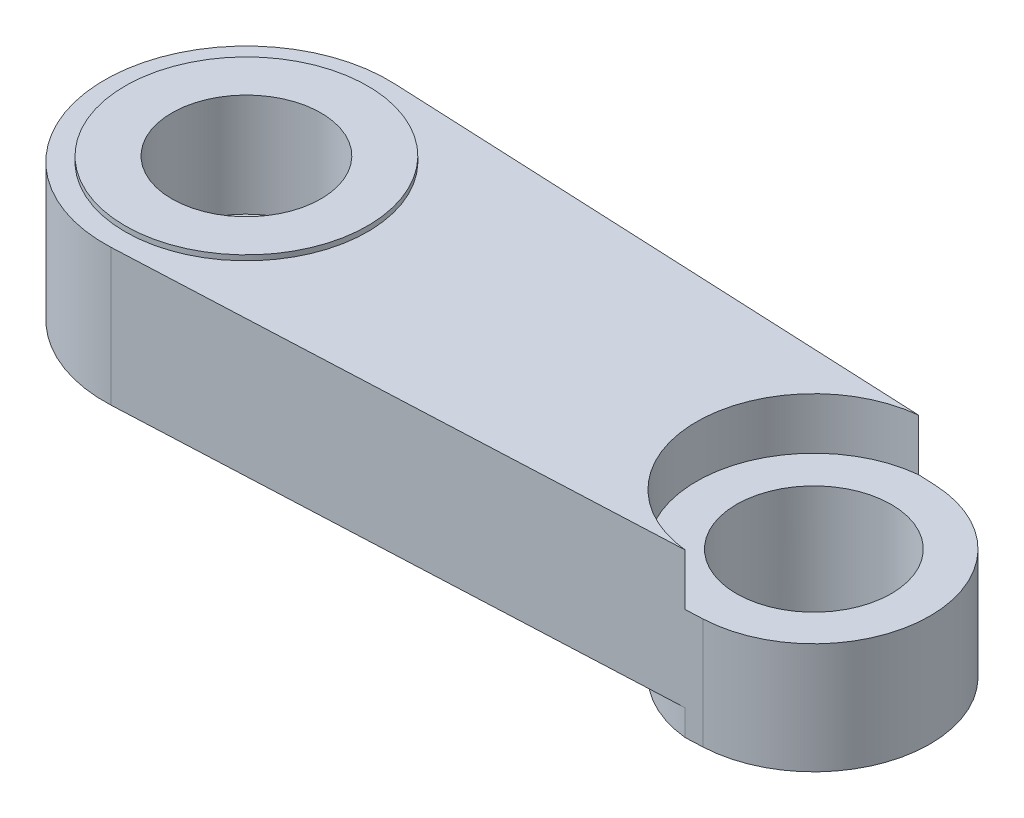
SolidWorks part; units mm, degrees
ref_plane "Front Plane" through (0, 0, 0) normal (0, 0, 1) x (1, 0, 0)
ref_plane "Top Plane" through (0, 0, 0) normal (0, 1, 0) x (1, 0, 0)
ref_plane "Right Plane" through (0, 0, 0) normal (1, 0, 0) x (0, 0, -1)
sketch "Sketch1" plane through (0, 0, 0) normal (0, 1, 0) x (1, 0, 0)
  line L0 (0.25, 5.4943) -> (22.2045, 4.4953)
  line L1 (22.2045, -4.4953) -> (0.25, -5.4943)
  circle A0 centre (0, 0) radius 1.5
  circle A1 centre (22, 0) radius 3
  arc A2 (0.25, 5.4943) -> (0.25, -5.4943) centre (0, 0) ccw
  arc A3 (22.2045, 4.4953) -> (22.2045, -4.4953) centre (22, 0) cw
  dimension "D2" = 6
  dimension "D3" = 3
  dimension "D4" = 4.5
  dimension "D5" = 5.5
  dimension "D1" = 22
extrude "Boss-Extrude1" add sketch "Sketch1" along normal blind 3.5 contours A0 | A1 | L1 A2 L0 A3 region at (0, 0, 0) region at (22, 0, 0)
sketch "Sketch2" plane through (0, 3.5, 0) normal (0, 1, 0) x (1, 0, 0)
  circle A0 centre (0, 0) radius 2.89
  circle A3 centre (0, 0) radius 4.7
  dimension "D1" = 5.78
  dimension "D2" = 9.4
extrude "Boss-Extrude2" add sketch "Sketch2" along normal blind 3
sketch "Sketch3" plane through (0, 3.5, 0) normal (0, 1, 0) x (1, 0, 0)
  circle A0 centre (0, 0) radius 2.89 construction
  circle A1 centre (0, 0) radius 2.89
extrude "Cut-Extrude1" cut sketch "Sketch3" against normal blind 1
sketch "Sketch4" plane through (0, 3.5, 0) normal (0, 1, 0) x (1, 0, 0)
  line L2 (22.2045, 4.4953) -> (0.25, 5.4943)
  line L3 (0.25, -5.4943) -> (22.2045, -4.4953)
  line L4 (22.2045, 4.4953) -> (0.25, 5.4943)
  line L5 (0.25, -5.4943) -> (22.2045, -4.4953)
  circle A1 centre (0, 0) radius 1.5 construction
  arc A2 (22.2045, -4.4953) -> (22.2045, 4.4953) centre (22, 0) ccw
  arc A3 (0.25, 5.4943) -> (0.25, -5.4943) centre (0, 0) ccw
  arc A4 (22.2045, -4.4953) -> (22.2045, 4.4953) centre (22, 0) ccw
  arc A5 (0.25, 5.4943) -> (0.25, -5.4943) centre (0, 0) ccw
  circle A6 centre (0, 0) radius 1.5
  circle A7 centre (22, 0) radius 3 construction
  circle A8 centre (22, 0) radius 3
  circle A9 centre (0, 0) radius 2.89 construction
  circle A10 centre (0, 0) radius 2.89
  circle M8 centre (0, 0) radius 4.7
  arc M9 (22.2045, -4.4953) -> (22.2045, 4.4953) centre (22, 0) ccw
  line M10 (22.2045, 4.4953) -> (0.25, 5.4943)
  arc M11 (0.25, 5.4943) -> (0.25, -5.4943) centre (0, 0) ccw
  line M12 (0.25, -5.4943) -> (22.2045, -4.4953)
  circle M13 centre (22, 0) radius 3
  dimension "D1" = 0
extrude "Boss-Extrude3" add sketch "Sketch4" along normal blind 1.8 contours M12 M9 M10 M11 M13 M8 region at (11.7364, 3.5, 0)
sketch "Sketch5" plane through (0, 0, 0) normal (0, -1, 0) x (1, 0, 0)
  line L2 (22.2045, 4.4953) -> (0.25, 5.4943)
  line L3 (0.25, -5.4943) -> (22.2045, -4.4953)
  line L4 (22.2045, 4.4953) -> (0.25, 5.4943)
  line L5 (0.25, -5.4943) -> (22.2045, -4.4953)
  arc A2 (22.2045, -4.4953) -> (22.2045, 4.4953) centre (22, 0) ccw
  arc A3 (0.25, 5.4943) -> (0.25, -5.4943) centre (0, 0) ccw
  arc A4 (22.2045, -4.4953) -> (22.2045, 4.4953) centre (22, 0) ccw
  arc A5 (0.25, 5.4943) -> (0.25, -5.4943) centre (0, 0) ccw
  dimension "D1" = 0
extrude "Cut-Extrude2" cut sketch "Sketch5" against normal blind 1
sketch "Sketch6" plane through (0, 5.3, 0) normal (0, 1, 0) x (1, 0, 0)
  line L0 (0.25, -5.4943) -> (22.2045, -4.4953) construction
  line L2 (22.2045, 4.4953) -> (0.25, 5.4943) construction
  line L5 (0.25, -5.4943) -> (22.2045, -4.4953)
  line L6 (22.2045, 4.4953) -> (0.25, 5.4943)
  line L7 (0.25, -5.4943) -> (22.8765, -4.4648)
  line L8 (22.8765, 4.4648) -> (0.25, 5.4943)
  arc A0 (22.8765, -4.4648) -> (22.8765, 4.4648) centre (22, 0) cw
  arc A2 (22.2045, -4.4953) -> (22.2045, 4.4953) centre (22, 0) ccw construction
  arc A3 (22.2045, -4.4953) -> (22.2045, 4.4953) centre (22, 0) ccw
  arc A4 (0.25, 5.4943) -> (0.25, -5.4943) centre (0, 0) ccw
  arc A6 (0.25, 5.4943) -> (0.25, -5.4943) centre (0, 0) ccw
  circle A7 centre (22, 0) radius 3 construction
  line M5 (0.25, -5.4943) -> (22.2045, -4.4953)
  arc M8 (0.25, 5.4943) -> (0.25, -5.4943) centre (0, 0) ccw
  circle M10 centre (0, 0) radius 4.7
  dimension "D1" = 4.55
  dimension "D2" = 0
extrude "Boss-Extrude4" add sketch "Sketch6" along normal blind 1 contours A0 L8 M5 M8 M10 region at (9.5191, 5.3, 0)
sketch "Sketch7" plane through (0, 5.3, 0) normal (0, 1, 0) x (1, 0, 0)
  line L2 (22.2045, 4.4953) -> (21.5326, 4.5259)
  line L3 (21.5326, -4.5259) -> (22.2045, -4.4953)
  line L4 (22.2045, 4.4953) -> (21.5326, 4.5259)
  line L5 (21.5326, -4.5259) -> (22.2045, -4.4953)
  circle A0 centre (22, 0) radius 3 construction
  circle A1 centre (22, 0) radius 3
  arc A2 (21.5326, 4.5259) -> (21.5326, -4.5259) centre (22, 0) ccw
  arc A3 (22.2045, -4.4953) -> (22.2045, 4.4953) centre (22, 0) ccw
  arc A4 (21.5326, 4.5259) -> (21.5326, -4.5259) centre (22, 0) ccw
  arc A5 (22.2045, -4.4953) -> (22.2045, 4.4953) centre (22, 0) ccw
  dimension "D1" = 0
extrude "Cut-Extrude3" cut sketch "Sketch7" against normal blind 1
extrude "Boss-Extrude5" add sketch "Sketch7<2>" against normal blind 1 from surface starting at face at (0, 1, -1.5)
sketch "Sketch7<2>" plane through (0, 5.3, 0) normal (0, 1, 0) x (1, 0, 0) same geometry as "Sketch7"
